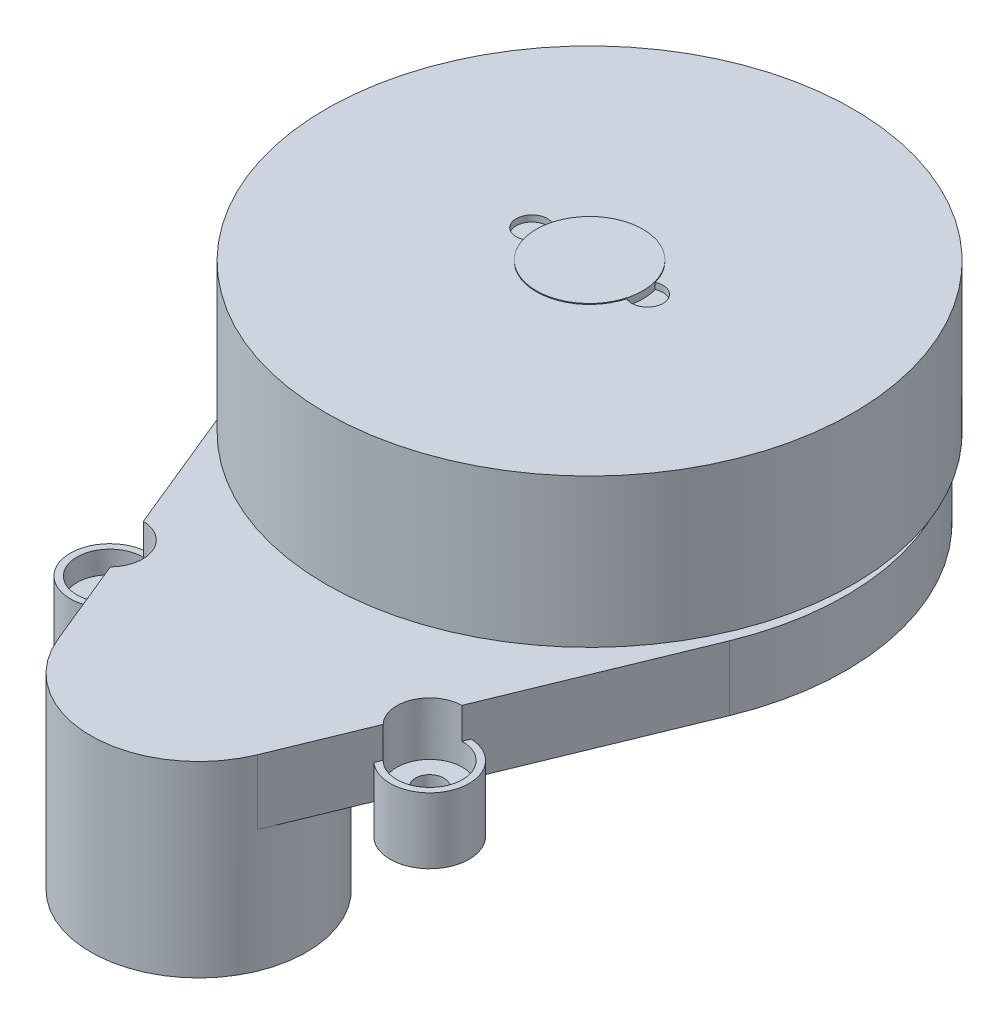
SolidWorks part; units mm, degrees
ref_plane "前视基准面" through (0, 0, 0) normal (0, 0, 1) x (1, 0, 0)
ref_plane "上视基准面" through (0, 0, 0) normal (0, 1, 0) x (1, 0, 0)
ref_plane "右视基准面" through (0, 0, 0) normal (1, 0, 0) x (0, 0, -1)
other "Configuration Table"
sketch "草图1" plane through (0, 0, 0) normal (0, 1, 0) x (1, 0, 0)
  line L0 (0, 0) -> (0, 77.1257) construction
sketch "草图2" plane through (0, 0, 0) normal (0, 1, 0) x (1, 0, 0)
  line L0 (0, 0) -> (0, 44)
  line L1 (0, -200000) -> (0, 200077.1257) construction
  line L2 (26.6912, 33.0501) -> (11.2409, -4.6115)
  line L3 (-26.6912, 33.0501) -> (-11.2409, -4.6115)
  arc A1 (26.6912, 33.0501) -> (-26.6912, 33.0501) centre (0, 44) ccw
  arc A2 (-11.2409, -4.6115) -> (11.2409, -4.6115) centre (0, 0) ccw
  dimension "D1" = 44
  dimension "D2" = 28.85
  dimension "D3" = 12.15
extrude "凸台-拉伸1" add sketch "草图2" along normal blind 7.3 contours L3 A2 L2 A1 region at (18.0156, 0, -14.6092)
sketch "草图3" plane through (0, 0, 0) normal (0, -1, 0) x (1, 0, 0)
  circle A0 centre (0, 0) radius 12.15
  dimension "D1" = 24.3
extrude "凸台-拉伸2" add sketch "草图3" along normal blind 13.8
sketch "草图4" plane through (0, -13.8, 0) normal (0, -1, 0) x (1, 0, 0)
  circle A0 centre (0, 0) radius 2.6535
  dimension "D1" = 5.3069
extrude "凸台-拉伸3" add sketch "草图4" along normal blind 0.5
sketch "草图5" plane through (0, 7.3, 0) normal (0, 1, 0) x (1, 0, 0)
  line L0 (0, 44) -> (0, 0) construction
  line L1 (4.4168, 79.5423) -> (5.2988, 72.3592)
  line L2 (-4.4168, 79.5423) -> (-5.2988, 72.3592)
  arc A0 (26.6912, 33.0501) -> (-26.6912, 33.0501) centre (0, 44) ccw construction
  arc A1 (26.6912, 33.0501) -> (-26.6912, 33.0501) centre (0, 44) ccw
  circle A2 centre (-18, 8) radius 4.45
  circle A4 centre (-18, 8) radius 3.7
  circle A5 centre (-18, 8) radius 1.6
  circle A6 centre (18, 8) radius 4.45
  circle A7 centre (18, 8) radius 1.6
  circle A8 centre (18, 8) radius 3.7
  circle A9 centre (0, 79) radius 4.45
  circle A10 centre (0, 79) radius 3.7
  circle A11 centre (0, 79) radius 1.6
  arc A12 (26.6912, 33.0501) -> (-26.6912, 33.0501) centre (0, 44) ccw construction
  point P13 (6.1995, 72.176)
  point P23 (5.5906, 72.3031)
  line M1 (-26.6912, 33.0501) -> (-11.2409, -4.6115)
  line M3 (11.2409, -4.6115) -> (26.6912, 33.0501)
  dimension "D3" = 8.9
  dimension "D4" = 7.4
  dimension "D5" = 3.2
  dimension "D6" = 7.4
  dimension "D7" = 3.2
  dimension "D8" = 8.9
  dimension "D10" = 7
  dimension "D1" = 36
  dimension "D2" = 36
  dimension "D9" = 35
extrude "切除-拉伸4" cut sketch "草图5" against normal through all both and the other way through all contours A5 M1 | A5 A4 M1 | A7 M3 | A8 A7 M3 | A5 region at (15.7821, 7.3, -8.9099) region at (16.5935, 7.3, -8.577) region at (-15.7821, 7.3, -8.9099) region at (-16.5935, 7.3, -8.577)
extrude "凸台-拉伸4" add sketch "草图5<6>" against normal blind 7.4 from offset 3.5 contours A4 A2 M1 | A4 A2 M1 region at (-15.001, 7.3, -11.1636) region at (-18.192, 7.3, -12.0276) offset against normal yes
sketch "草图5<6>" plane through (0, 7.3, 0) normal (0, 1, 0) x (1, 0, 0) same geometry as "草图5"
extrude "凸台-拉伸5" add sketch "草图5<7>" against normal blind 3.2 from offset 6 contours A5 A4 M1 | A5 A4 M1 region at (-17.4991, 7.3, -10.3867) region at (-15.7821, 7.3, -8.9099) offset against normal yes
sketch "草图5<7>" plane through (0, 7.3, 0) normal (0, 1, 0) x (1, 0, 0) same geometry as "草图5"
mirror "镜向1" about plane through (0, 0, 0) normal (1, 0, 0) of "凸台-拉伸5", "凸台-拉伸4"
sketch "草图6" plane through (0, 0, 0) normal (0, -1, 0) x (1, 0, 0)
  line L0 (15.8, -20.5) -> (-15.8, -20.5)
  line L1 (0, -44) -> (0, 0) construction
  line L2 (-15.8, -20.5) -> (-20.435, -23.599)
  line L3 (-20.435, -23.599) -> (-24.1227, -33.466)
  line L4 (-24.1227, -33.466) -> (-24.1227, -55.7894)
  line L5 (-4.3179, -70.5) -> (4.3179, -70.5)
  line L6 (0, 0) -> (0, -44) construction
  line L7 (24.1227, -33.466) -> (24.1227, -55.7894)
  line L8 (20.435, -23.599) -> (24.1227, -33.466)
  line L9 (15.8, -20.5) -> (20.435, -23.599)
  arc A0 (-24.1227, -55.7894) -> (-4.3179, -70.5) centre (0, -44) ccw
  arc A1 (24.1227, -55.7894) -> (4.3179, -70.5) centre (0, -44) cw
  point P15 (0, -70.5)
  point P19 (0, -20.5)
  dimension "D3" = 26.5
  dimension "D5" = 33.767
  dimension "D9" = 26.8495
  dimension "D1" = 23.5
  dimension "D2" = 15.8
  dimension "D4" = 26.5
  dimension "D6" = 24.1227
  dimension "D7" = 10.5336
  dimension "D8" = 5.5756
extrude "凸台-拉伸6" add sketch "草图6" along normal blind 0.7
sketch "草图7" plane through (0, -0.7, 0) normal (0, -1, 0) x (1, 0, 0)
  line L0 (0, -20.5) -> (0, -57.5222) construction
  line L1 (-10.45, -23.2) -> (-6.2, -23.2)
  line L2 (-10.45, -23.2) -> (-10.45, -31.5)
  line L3 (-10.45, -31.5) -> (-6.2, -31.5)
  line L4 (-6.2, -23.2) -> (-6.2, -31.5)
  line L5 (15.8, -20.5) -> (-15.8, -20.5) construction
  dimension "D1" = 4.25
  dimension "D2" = 8.3
  dimension "D3" = 6.2
  dimension "D4" = 2.7
extrude "凸台-拉伸7" add sketch "草图7" along normal blind 3.8
sketch "草图8" plane through (-10.45, 0, 0) normal (-1, 0, 0) x (0, 0, 1)
  line L0 (-27.35, -4.5) -> (-27.35, -0.7) construction
  line L1 (-23.2, -4.5) -> (-31.5, -4.5) construction
  line L2 (-23.2, -0.7) -> (-31.5, -0.7) construction
  line L3 (-30.45, -4.2423) -> (-30.45, -3.0423)
  line L4 (-30.45, -3.0423) -> (-28.225, -3.0423)
  line L5 (-28.225, -3.0423) -> (-28.225, -3.3637)
  line L6 (-28.225, -3.3637) -> (-26.475, -3.3637)
  line L7 (-30.45, -4.2423) -> (-24.25, -4.2423)
  line L8 (-26.475, -3.0423) -> (-26.475, -3.3637)
  line L9 (-24.25, -3.0423) -> (-26.475, -3.0423)
  line L10 (-24.25, -4.2423) -> (-24.25, -3.0423)
  point P13 (-27.35, -4.2423)
  point P14 (-27.35, -3.3637)
  dimension "D1" = 3.1
  dimension "D2" = 0.2577
  dimension "D3" = 1.2
  dimension "D4" = 0.3214
  dimension "D5" = 0.875
extrude "切除-拉伸5" cut sketch "草图8" against normal through all and the other way through all
sketch "草图9" plane through (-6.2, 0, 0) normal (1, 0, 0) x (0, 0, -1)
  line L0 (26.475, -3.0423) -> (28.225, -3.0423)
  line L1 (28.225, -3.0423) -> (28.225, -3.3637)
  line L2 (26.475, -3.3637) -> (28.225, -3.3637) construction
  line L3 (28.225, -3.3637) -> (26.475, -3.3637)
  line L4 (26.475, -3.3637) -> (26.475, -3.0423)
extrude "切除-拉伸6" cut sketch "草图9" against normal blind 2
sketch "草图10" plane through (-10.45, 0, 0) normal (-1, 0, 0) x (0, 0, 1)
  line L0 (-28.225, -3.0423) -> (-26.475, -3.0423)
  line L1 (-26.475, -3.0423) -> (-26.475, -3.3637)
  line L2 (-26.475, -3.3637) -> (-28.225, -3.3637)
  line L3 (-28.225, -3.3637) -> (-28.225, -3.0423)
  line L4 (-27.35, -0.7) -> (-27.35, -4.5) construction
  line L5 (-23.2, -0.7) -> (-31.5, -0.7) construction
  line L6 (-23.2, -4.5) -> (-31.5, -4.5) construction
  line L7 (-23.7546, -0.95) -> (-30.9454, -0.95)
  line L8 (-30.9454, -0.95) -> (-30.9454, -3.2842)
  line L9 (-30.9454, -3.2842) -> (-30.6899, -3.2842)
  line L10 (-30.6899, -2.7042) -> (-24.0101, -2.7042)
  line L11 (-30.6899, -3.2842) -> (-30.6899, -2.7042)
  line L12 (-23.599, -0.7) -> (-33.466, -0.7) construction
  line L13 (-24.0101, -3.2842) -> (-24.0101, -2.7042)
  line L14 (-23.7546, -3.2842) -> (-24.0101, -3.2842)
  line L15 (-23.7546, -0.95) -> (-23.7546, -3.2842)
  point P22 (0, 0)
  point P23 (0, 0)
  point P26 (-27.35, -2.7042)
  point P28 (-27.35, -0.95)
  line M9 (-28.225, -3.0423) -> (-28.225, -3.3637)
  line M10 (-28.225, -3.3637) -> (-26.475, -3.3637)
  line M11 (-26.475, -3.3637) -> (-26.475, -3.0423)
  dimension "D1" = 3.5954
  dimension "D2" = 0.25
  dimension "D3" = 0.58
  dimension "D4" = 0.2555
  dimension "D5" = 1.7542
extrude "切除-拉伸7" cut sketch "草图10" against normal blind 2 contours L4 L7 L8 L9 L11 L10 | L7 L4 L10 L13 L14 L15 region at (-10.45, -1.8539, -29.186) region at (-10.45, -1.8539, -25.514)
extrude "切除-拉伸8" cut sketch "草图10<3>" against normal blind 0.3 contours L4 L0 M9 M10 | L0 L4 L2 M11 region at (-10.45, -3.203, -27.7875) region at (-10.45, -3.203, -26.9125)
sketch "草图10<3>" plane through (-10.45, 0, 0) normal (-1, 0, 0) x (0, 0, 1) same geometry as "草图10"
sketch "草图11" plane through (0, 7.3, 0) normal (0, 1, 0) x (1, 0, 0)
  line L0 (4.4168, 79.5423) -> (5.2988, 72.3592) construction
  line L1 (-4.4168, 79.5423) -> (-5.2988, 72.3592) construction
  line L2 (4.4168, 79.5423) -> (5.2988, 72.3592)
  line L3 (-4.4168, 79.5423) -> (-5.2988, 72.3592)
  arc A0 (26.6912, 33.0501) -> (-26.6912, 33.0501) centre (0, 44) ccw construction
  circle A1 centre (0, 79) radius 1.6 construction
  circle A2 centre (0, 79) radius 3.7 construction
  circle A3 centre (0, 79) radius 4.45 construction
  arc A4 (26.6912, 33.0501) -> (-26.6912, 33.0501) centre (0, 44) ccw
  circle A5 centre (0, 79) radius 1.6
  circle A6 centre (0, 79) radius 3.7
  circle A7 centre (0, 79) radius 4.45
  arc M4 (26.6912, 33.0501) -> (-26.6912, 33.0501) centre (0, 44) ccw
extrude "凸台-拉伸8" add sketch "草图11" against normal up to surface (7.3 mm away) from offset 3.5 contours A7 L3 L2 M4 region at (0, 7.3, -74.3756) up to face at (0, 0, -18.7412) offset against normal yes
extrude "凸台-拉伸9" add sketch "草图11<3>" against normal blind 7.4 from offset 3.5 contours A7 A6 region at (4.3161, 7.3, -79.264) offset against normal yes
sketch "草图11<3>" plane through (0, 7.3, 0) normal (0, 1, 0) x (1, 0, 0) same geometry as "草图11"
extrude "凸台-拉伸10" add sketch "草图11<4>" against normal blind 3.2 from offset 6 contours A6 A5 region at (-3.5953, 7.3, -79) offset against normal yes
sketch "草图11<4>" plane through (0, 7.3, 0) normal (0, 1, 0) x (1, 0, 0) same geometry as "草图11"
sketch "草图12" plane through (0, 7.3, 0) normal (0, 1, 0) x (1, 0, 0)
  arc A0 (26.6912, 33.0501) -> (-26.6912, 33.0501) centre (0, 44) ccw construction
  arc A1 (26.6912, 33.0501) -> (-26.6912, 33.0501) centre (0, 44) ccw
  circle A2 centre (0, 44) radius 25
  dimension "D1" = 50
extrude "凸台-拉伸11" add sketch "草图12" along normal blind 1.5 contours A2 region at (0, 7.3, -44)
sketch "草图13" plane through (0, 8.8, 0) normal (0, 1, 0) x (1, 0, 0)
  circle A0 centre (0, 44) radius 25 construction
  circle A1 centre (0, 44) radius 25
  circle A2 centre (0, 44) radius 29.65
  circle M1 centre (0, 44) radius 25
  dimension "D1" = 59.3
extrude "凸台-拉伸12" add sketch "草图13" along normal blind 16.7 contours M1 | A2 M1 region at (0, 8.8, -44) region at (-28.8114, 8.8, -44)
sketch "草图14" plane through (0, 25.5, 0) normal (0, 1, 0) x (1, 0, 0)
  line L0 (0, 57.9851) -> (0, 28.8444) construction
  circle A0 centre (0, 44) radius 29.65 construction
  circle A1 centre (0, 44) radius 29.65
  circle A2 centre (0, 44) radius 6
  arc A3 (5.7802, 45.609) -> (5.7802, 42.391) centre (6.5, 44) cw
  arc A4 (-5.7802, 45.609) -> (-5.7802, 42.391) centre (-6.5, 44) ccw
  point P10 (0, 0)
  point P11 (0, 0)
  dimension "D1" = 12
  dimension "D3" = 1.7626
  dimension "D2" = 6.5
extrude "切除-拉伸9" cut sketch "草图14" against normal blind 0.7 contours A2 A4 | A3 A2 region at (6.9476, 25.5, -44) region at (-6.9476, 25.5, -44)
extrude "凸台-拉伸13" add sketch "草图14<3>" along normal blind 0.1 contours L0 A2 | A2 L0 region at (2.5465, 25.5, -44) region at (-2.5465, 25.5, -44)
sketch "草图14<3>" plane through (0, 25.5, 0) normal (0, 1, 0) x (1, 0, 0) same geometry as "草图14"
equation "\"7.37.25mm\"=7.25"
